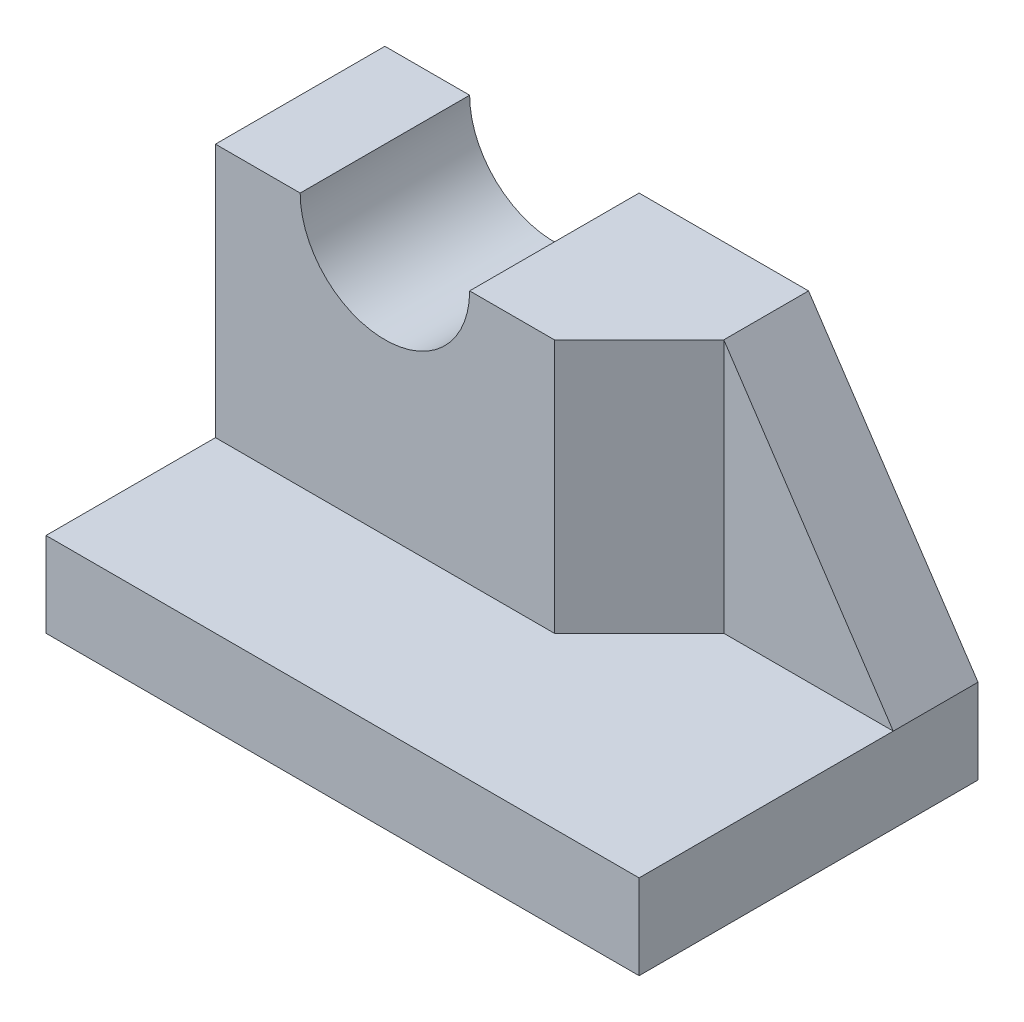
SolidWorks part; units mm, degrees
ref_plane "前基準面" through (0, 0, 0) normal (0, 0, 1) x (1, 0, 0)
ref_plane "上基準面" through (0, 0, 0) normal (0, 1, 0) x (1, 0, 0)
ref_plane "右基準面" through (0, 0, 0) normal (1, 0, 0) x (0, 0, -1)
sketch "草圖1" plane through (0, 0, 0) normal (0, 1, 0) x (1, 0, 0)
  line L0 (2.5, 0) -> (7.5, 5)
  line L1 (-17.5, -10) -> (17.5, -10)
  line L2 (-17.5, -10) -> (-17.5, 10)
  line L3 (-17.5, 10) -> (17.5, 10)
  line L4 (17.5, -10) -> (17.5, 10)
  line L5 (-17.5, -10) -> (17.5, 10) construction
  line L6 (-17.5, 10) -> (17.5, -10) construction
  line L7 (-17.5, 10) -> (-12.5, 10)
  line L8 (-17.5, 10) -> (-17.5, 0)
  line L9 (-17.5, 0) -> (-12.5, 0)
  line L10 (-12.5, 10) -> (-12.5, 0)
  line L11 (-12.5, 0) -> (2.5, 0)
  line L12 (-12.5, 0) -> (-12.5, 10)
  line L13 (-12.5, 10) -> (7.5, 10)
  line L14 (7.5, 5) -> (7.5, 10)
  line L15 (7.5, 10) -> (17.5, 10)
  line L16 (7.5, 10) -> (7.5, 5)
  line L17 (7.5, 5) -> (17.5, 5)
  line L18 (17.5, 10) -> (17.5, 5)
  point P0 (0, 0)
  point P10 (7.5, 0)
  dimension "D1" = 20
  dimension "D2" = 35
  dimension "D3" = 5
  dimension "D4" = 10
  dimension "D5" = 5
  dimension "D6" = 10
extrude "填料-伸長1" add sketch "草圖1" along normal blind 5 contours L10 L3 L2 L9 | L0 L14 L3 L10 L11 | L17 L0 L11 L9 L2 L1 L4 | L14 L17 L4 L3 region at (-3.0556, 0, -5.2222) region at (1.6919, 0, 3.8889) region at (12.5, 0, -7.5) region at (-15, 0, -5)
extrude "填料-伸長2" add sketch "草圖1<3>" along normal blind 20 contours L10 L3 L2 L9 | L0 L14 L3 L10 L11 | L14 L17 L4 L3 region at (-3.0556, 0, -5.2222) region at (12.5, 0, -7.5) region at (-15, 0, -5)
sketch "草圖1<3>" plane through (0, 0, 0) normal (0, 1, 0) x (1, 0, 0) same geometry as "草圖1"
sketch "草圖2" plane through (0, 0, 0) normal (0, 0, 1) x (1, 0, 0)
  line L0 (-7.5, 20) -> (-7.5, 11.813) construction
  line L1 (-17.5, 20) -> (2.5, 20) construction
  line L2 (-17.5, 20) -> (-17.5, 5) construction
  line L3 (-12.5, 20) -> (-2.5, 20)
  line L4 (17.5, 5) -> (7.5, 20)
  line L5 (7.5, 20) -> (17.5, 20) construction
  line L6 (7.5, 20) -> (17.5, 20)
  line L7 (17.5, 20) -> (17.5, 5) construction
  line L8 (17.5, 20) -> (17.5, 5)
  arc A0 (-12.5, 20) -> (-2.5, 20) centre (-7.5, 20) ccw
  dimension "D2" = 10
  dimension "D1" = 10
  dimension "D3" = 10
extrude "除料-伸長1" cut sketch "草圖2" against normal blind 20
scale "縮放比例1" scale about centroid uniform scaling yes scale factor 0.2
